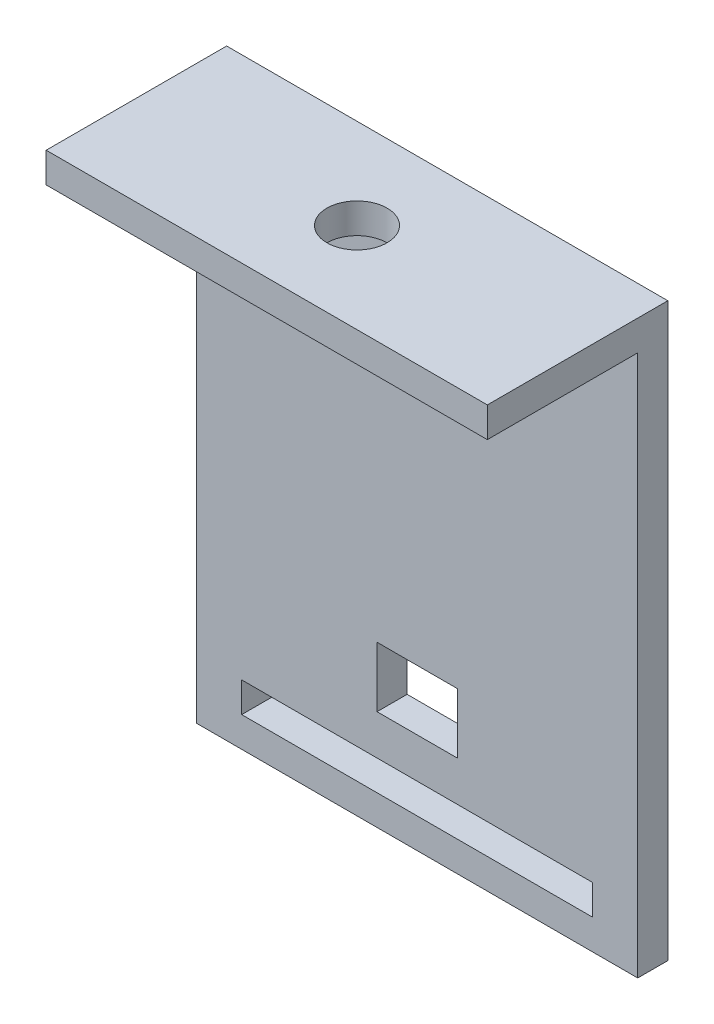
SolidWorks part; units mm, degrees
ref_plane "Piano frontale" through (0, 0, 0) normal (0, 0, 1) x (1, 0, 0)
ref_plane "Piano superiore" through (0, 0, 0) normal (0, 1, 0) x (1, 0, 0)
ref_plane "Piano destro" through (0, 0, 0) normal (1, 0, 0) x (0, 0, -1)
sketch "Schizzo8" plane through (0, 0, 0) normal (1, 0, 0) x (0, 0, -1)
  line L0 (0, 0) -> (0, 3)
  line L1 (0, 3) -> (18, 3)
  line L2 (18, 3) -> (18, -54)
  line L3 (18, -54) -> (15, -54)
  line L4 (15, -54) -> (15, 0)
  line L5 (15, 0) -> (0, 0)
  dimension "D1" = 3
  dimension "D2" = 18
  dimension "D3" = 54
  dimension "D4" = 3
extrude "Estrusione-Estrusione6" add sketch "Schizzo8" along normal blind 44
sketch "Schizzo9" plane through (0, 0, -15) normal (0, 0, 1) x (1, 0, 0)
  line L0 (44, -54) -> (0, -54) construction
  line L1 (4.5, -51) -> (39.5, -51)
  line L2 (4.5, -51) -> (4.5, -48)
  line L3 (4.5, -48) -> (39.5, -48)
  line L4 (39.5, -51) -> (39.5, -48)
  line L5 (0, 0) -> (0, -54) construction
  dimension "D1" = 3
  dimension "D2" = 35
  dimension "D3" = 3
  dimension "D4" = 4.5
extrude "Taglio-Estrusione2" cut sketch "Schizzo9" against normal blind 44
sketch "Schizzo10" plane through (0, 3, 0) normal (0, 1, 0) x (1, 0, 0)
  line L0 (0, 18) -> (44, 0) construction
  line L1 (44, 18) -> (44, 0) construction
  line L2 (44, 0) -> (44, 18) construction
  line L3 (44, 18) -> (0, 0) construction
  circle A0 centre (22, 9) radius 3
  dimension "D1" = 6
extrude "Taglio-Estrusione3" cut sketch "Schizzo10" against normal blind 10
sketch "Schizzo11" plane through (0, 0, -18) normal (0, 0, -1) x (-1, 0, 0)
  line L0 (-22, -48) -> (-22, -44) construction
  line L1 (-39.5, -48) -> (-4.5, -48) construction
  line L2 (-26, -44) -> (-18, -44)
  line L3 (-26, -44) -> (-26, -38)
  line L4 (-26, -38) -> (-18, -38)
  line L5 (-18, -38) -> (-18, -44)
  point P7 (-22, -44)
  dimension "D1" = 4
  dimension "D2" = 8
  dimension "D3" = 6
extrude "Taglio-Estrusione4" cut sketch "Schizzo11" against normal blind 10
